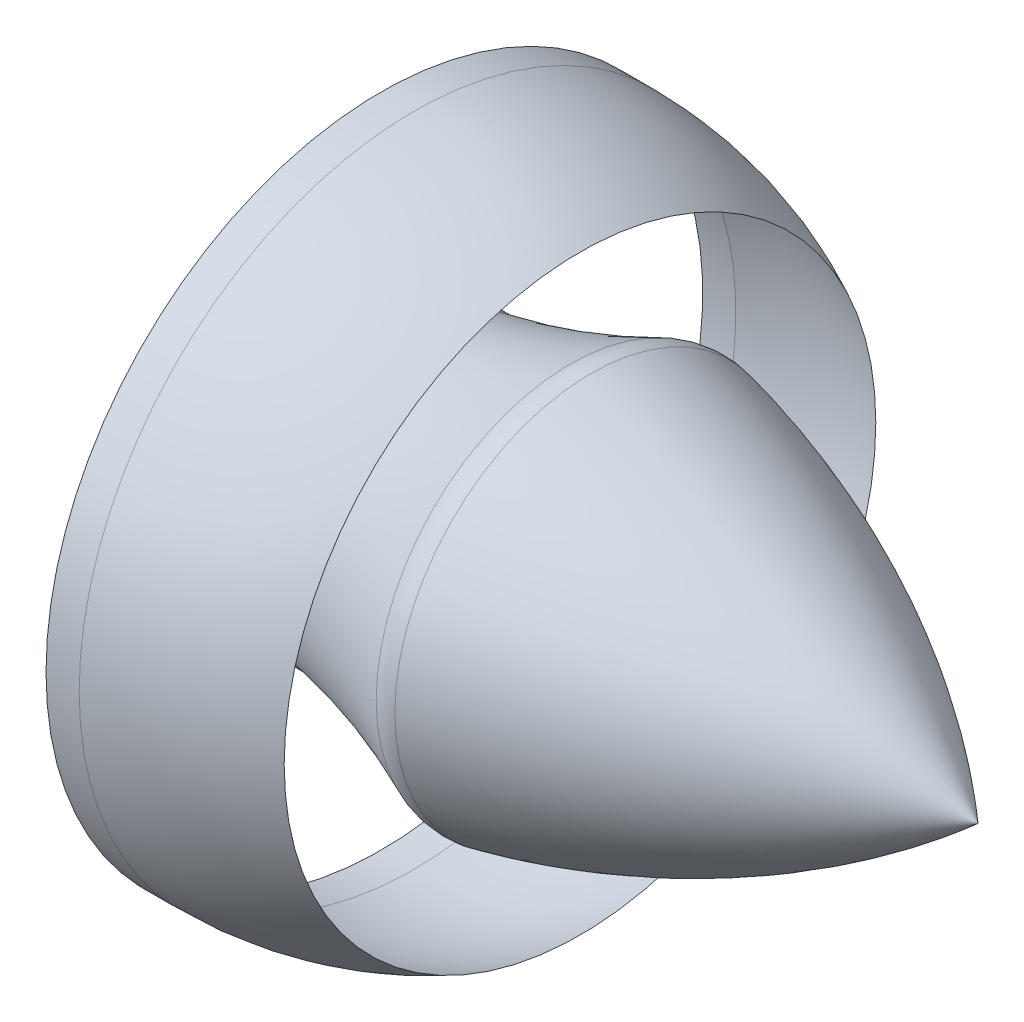
SolidWorks part; units mm, degrees
material "AISI 316 Stainless Steel Sheet (SS)"
ref_plane "Front Plane" through (0, 0, 0) normal (0, 0, 1) x (1, 0, 0)
ref_plane "Top Plane" through (0, 0, 0) normal (0, 1, 0) x (1, 0, 0)
ref_plane "Right Plane" through (0, 0, 0) normal (1, 0, 0) x (0, 0, -1)
sketch "Sketch2" plane through (0, 0, 0) normal (0, 0, 1) x (1, 0, 0)
  line L0 (-2128.6318, 0) -> (104302.9566, 0) construction
  line L1 (30, 29.9255) -> (30, 27.6174)
  line L2 (0, 50.5) -> (5, 50.5)
  line L3 (0, 50.5) -> (0, 48.5)
  line L4 (0, 48.5) -> (5, 48.5)
  line L6 (0, 22) -> (5, 22)
  line L7 (0, 22) -> (0, 20)
  line L8 (0, 20) -> (5, 20)
  line L9 (5, 22) -> (5, 20)
  line L10 (88.8076, 0) -> (90, 0)
  line L12 (0, 22) -> (-21, 22)
  line L13 (0, 22) -> (0, 20)
  line L14 (0, 20) -> (-21, 20)
  line L15 (-21, 22) -> (-21, 20)
  arc A0 (5, 48.5) -> (30, 44.5961) centre (10.0367, -1.2457) cw
  arc A1 (5, 50.5) -> (30, 44.5961) centre (5.2086, -4.4996) cw
  arc A2 (5, 22) -> (30, 29.9255) centre (-12.459, 120.4641) ccw
  arc A3 (5, 20) -> (30, 27.6174) centre (-29.5627, 178.2675) ccw
  arc A4 (30, 29.9255) -> (90, 0) centre (3.6333, -98.0512) cw
  arc A5 (30, 27.6174) -> (88.8076, 0) centre (-1.8786, -116.6841) cw
  point P21 (2.5, 20)
  dimension "D5" = 50
  dimension "D6" = 55
  dimension "D10" = 100
  dimension "D11" = 60
  dimension "D1" = 48.5
  dimension "D2" = 2
  dimension "D3" = 5
  dimension "D4" = 30
  dimension "D7" = 5
  dimension "D8" = 20
  dimension "D9" = 2
  dimension "D12" = 21
revolve "Revolve3" add sketch "Sketch2" angle 360 about L0 region at (61.6529, 18.2768, 0) region at (17.8137, 24.5087, 0) region at (2.5, 21, 0) region at (-10.5, 21, 0)
fillet "Fillet1" radius 5 2 edges at (5, 0, 22) (-21, 0, 22)
fillet "Fillet2" radius 5 1 edges at (30, 0, 29.9255)
